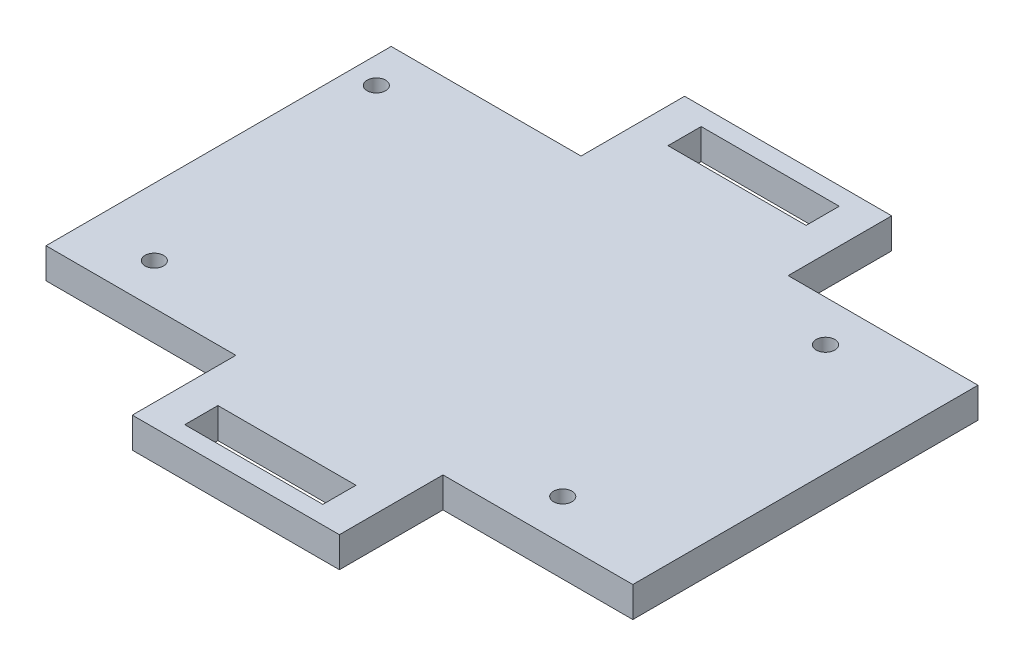
SolidWorks part; units mm, degrees
ref_plane "Front Plane" through (0, 0, 0) normal (0, 0, 1) x (1, 0, 0)
ref_plane "Top Plane" through (0, 0, 0) normal (0, 1, 0) x (1, 0, 0)
ref_plane "Right Plane" through (0, 0, 0) normal (1, 0, 0) x (0, 0, -1)
sketch "Sketch1" plane through (0, 0, 0) normal (0, 1, 0) x (1, 0, 0)
  line L0 (19.05, 31.75) -> (19.05, 50.8)
  line L1 (-53.975, -31.75) -> (-19.05, -31.75)
  line L2 (-53.975, -31.75) -> (-53.975, 31.75)
  line L3 (-53.975, 31.75) -> (-19.05, 31.75)
  line L4 (53.975, -31.75) -> (53.975, 31.75)
  line L5 (-53.975, -31.75) -> (53.975, 31.75) construction
  line L6 (-53.975, 31.75) -> (53.975, -31.75) construction
  line L7 (19.05, 50.8) -> (-19.05, 50.8)
  line L8 (-19.05, 50.8) -> (-19.05, 31.75)
  line L9 (19.05, 31.75) -> (53.975, 31.75)
  line L10 (-53.975, 0) -> (53.975, 0) construction
  line L11 (19.05, -31.75) -> (19.05, -50.8)
  line L12 (19.05, -50.8) -> (-19.05, -50.8)
  line L13 (-19.05, -50.8) -> (-19.05, -31.75)
  line L14 (19.05, -31.75) -> (53.975, -31.75)
  point P0 (0, 0)
  dimension "D1" = 107.95
  dimension "D2" = 63.5
  dimension "D3" = 19.05
  dimension "D4" = 38.1
extrude "Boss-Extrude1" add sketch "Sketch1" along normal blind 5.588
sketch "Sketch2" plane through (0, 5.588, 0) normal (0, 1, 0) x (1, 0, 0)
  line L0 (0, 0) -> (53.975, 0) construction
  line L1 (-12.7, 41.402) -> (12.7, 41.402)
  line L2 (-12.7, 41.402) -> (-12.7, 47.498)
  line L3 (-12.7, 47.498) -> (12.7, 47.498)
  line L4 (12.7, 41.402) -> (12.7, 47.498)
  line L5 (-12.7, 41.402) -> (12.7, 47.498) construction
  line L6 (-12.7, 47.498) -> (12.7, 41.402) construction
  line L7 (53.975, -31.75) -> (53.975, 31.75) construction
  line L8 (-12.7, -47.498) -> (12.7, -41.402) construction
  line L9 (-12.7, -41.402) -> (12.7, -47.498) construction
  line L10 (12.7, -41.402) -> (12.7, -47.498)
  line L11 (-12.7, -47.498) -> (12.7, -47.498)
  line L12 (-12.7, -41.402) -> (-12.7, -47.498)
  line L13 (-12.7, -41.402) -> (12.7, -41.402)
  point P0 (0, 44.45)
  point P5 (0, 0)
  point P15 (0, -44.45)
  dimension "D1" = 6.096
  dimension "D2" = 25.4
  dimension "D3" = 41.402
extrude "Cut-Extrude1" cut sketch "Sketch2" against normal through all
sketch "Sketch3" plane through (0, 5.588, 0) normal (0, 1, 0) x (1, 0, 0)
  point P0 (-49.1236, 24.1681)
  point P1 (33.5026, 24.1681)
  point P3 (33.5026, -24.1681)
  point P5 (-41.6306, -24.1681)
hole_wizard "M3 Clearance Hole1" positions "Sketch4" profile "Sketch5" hole size "M3" standard "ANSI Metric" end condition through all
sketch "Sketch4" plane through (0, 5.588, 0) normal (0, 1, 0) x (1, 0, 0)
  point P0 (-49.1236, 24.1681)
  point P3 (33.5026, 24.1681)
  point P6 (33.5026, -24.1681)
  point P9 (-41.6306, -24.1681)
sketch "Sketch5" plane through (-49.1236, 5.588, -24.1681) normal (1, 0, 0) x (0, 0, 1)
  line L0 (0, 0) -> (0, 5.588)
  line L1 (0, 5.588) -> (1.7, 5.588)
  line L2 (1.7, 5.588) -> (1.7, 0)
  line L5 (1.7, 0) -> (0, 0)
  line L11 (0, -6.35) -> (0, 107.95) construction
  dimension "Thru Hole Dia." = 3.4
  dimension "Thru Hole Depth" = 5.588
